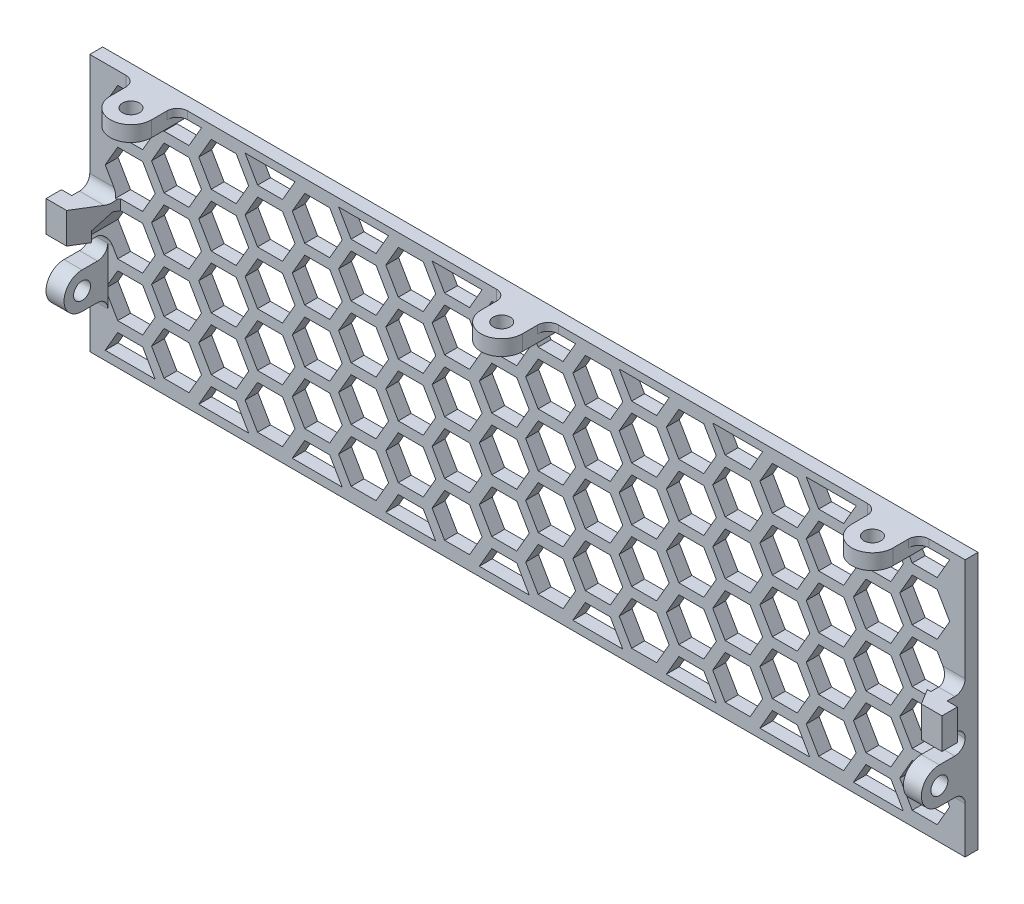
SolidWorks part; units mm, degrees
ref_plane "Plano frontal" through (0, 0, 0) normal (0, 0, 1) x (1, 0, 0)
ref_plane "Plano superior" through (0, 0, 0) normal (0, 1, 0) x (1, 0, 0)
ref_plane "Plano direito" through (0, 0, 0) normal (1, 0, 0) x (0, 0, -1)
sketch "Esboço1" plane through (0, 0, 0) normal (0, 0, 1) x (1, 0, 0)
  line L1 (-85, 25) -> (85, 25)
  line L2 (-85, 25) -> (-85, -25)
  line L3 (-85, -25) -> (85, -25)
  line L4 (85, 25) -> (85, -25)
  line L5 (-85, 25) -> (85, -25) construction
  line L6 (-85, -25) -> (85, 25) construction
  point P0 (0, 0)
  dimension "D1" = 170
  dimension "D2" = 50
extrude "Ressalto-extrusão1" add sketch "Esboço1" along normal blind 2.5
sketch "Esboço2" plane through (0, 0, 0) normal (0, 1, 0) x (1, 0, 0)
  line L0 (-85, -2.5) -> (-85, -6)
  line L1 (-85, -6) -> (-87, -6)
  line L2 (-87, -6) -> (-87, -9)
  line L3 (-87, -9) -> (-83, -9)
  line L4 (-83, -9) -> (-79, -2.5)
  line L5 (85, -2.5) -> (-85, -2.5) construction
  line L6 (85, 0) -> (-85, 0) construction
  line L7 (-83, -9) -> (-83, -2.5) construction
  line L8 (-83, -2.5) -> (-79, -2.5) construction
  line L9 (-85, -2.5) -> (-79, -2.5)
  line L10 (0, 0) -> (0, -20.2439) construction
  line L11 (83, -2.5) -> (79, -2.5) construction
  line L12 (83, -9) -> (83, -2.5) construction
  line L13 (85, -2.5) -> (79, -2.5)
  line L14 (83, -9) -> (79, -2.5)
  line L15 (87, -9) -> (83, -9)
  line L16 (87, -6) -> (87, -9)
  line L17 (85, -6) -> (87, -6)
  line L18 (85, -2.5) -> (85, -6)
  point P10 (-87, -7.5)
  dimension "D1" = 7.5
  dimension "D2" = 2
  dimension "D3" = 3
  dimension "D4" = 2
  dimension "D5" = 4
extrude "Ressalto-extrusão2" add sketch "Esboço2" along normal mid plane 6
sketch "Esboço3" plane through (0, 0, 0) normal (0, 0, -1) x (-1, 0, 0)
  line L0 (-72.3051, 23.5) -> (-70.5763, 22.5019) construction
  line L4 (-82, 23.5) -> (-79.5763, 19.302)
  line L5 (-79.5763, 19.302) -> (-74.7288, 19.302)
  line L6 (-74.7288, 19.302) -> (-72.3051, 23.5)
  line L7 (-63.3051, 18.3038) -> (-65.7288, 22.5019)
  line L8 (-65.7288, 22.5019) -> (-70.5763, 22.5019)
  line L9 (-70.5763, 22.5019) -> (-73, 18.3038)
  line L10 (-73, 18.3038) -> (-70.5763, 14.1058)
  line L11 (-70.5763, 14.1058) -> (-65.7288, 14.1058)
  line L12 (-65.7288, 14.1058) -> (-63.3051, 18.3038)
  line L13 (-85, 25) -> (85, 25) construction
  line L14 (63.3051, 23.5) -> (73, 23.5)
  line L15 (-73, 18.3038) -> (-80.4849, 18.3038) construction
  line L19 (-63.8369, 23.5) -> (-61.4131, 19.302)
  line L20 (-61.4131, 19.302) -> (-56.5657, 19.302)
  line L21 (-56.5657, 19.302) -> (-54.142, 23.5)
  line L22 (-45.142, 18.3038) -> (-47.5657, 22.5019)
  line L23 (-47.5657, 22.5019) -> (-52.4131, 22.5019)
  line L24 (-52.4131, 22.5019) -> (-54.8369, 18.3038)
  line L25 (-54.8369, 18.3038) -> (-52.4131, 14.1058)
  line L26 (-52.4131, 14.1058) -> (-47.5657, 14.1058)
  line L27 (-47.5657, 14.1058) -> (-45.142, 18.3038)
  line L31 (-45.6737, 23.5) -> (-43.25, 19.302)
  line L32 (-43.25, 19.302) -> (-38.4026, 19.302)
  line L33 (-38.4026, 19.302) -> (-35.9788, 23.5)
  line L34 (-26.9788, 18.3038) -> (-29.4026, 22.5019)
  line L35 (-29.4026, 22.5019) -> (-34.25, 22.5019)
  line L36 (-34.25, 22.5019) -> (-36.6737, 18.3038)
  line L37 (-36.6737, 18.3038) -> (-34.25, 14.1058)
  line L38 (-34.25, 14.1058) -> (-29.4026, 14.1058)
  line L39 (-29.4026, 14.1058) -> (-26.9788, 18.3038)
  line L43 (-27.5106, 23.5) -> (-25.0869, 19.302)
  line L44 (-25.0869, 19.302) -> (-20.2394, 19.302)
  line L45 (-20.2394, 19.302) -> (-17.8157, 23.5)
  line L46 (-8.8157, 18.3038) -> (-11.2394, 22.5019)
  line L47 (-11.2394, 22.5019) -> (-16.0869, 22.5019)
  line L48 (-16.0869, 22.5019) -> (-18.5106, 18.3038)
  line L49 (-18.5106, 18.3038) -> (-16.0869, 14.1058)
  line L50 (-16.0869, 14.1058) -> (-11.2394, 14.1058)
  line L51 (-11.2394, 14.1058) -> (-8.8157, 18.3038)
  line L55 (-9.3474, 23.5) -> (-6.9237, 19.302)
  line L56 (-6.9237, 19.302) -> (-2.0763, 19.302)
  line L57 (-2.0763, 19.302) -> (0.3474, 23.5)
  line L58 (9.3474, 18.3038) -> (6.9237, 22.5019)
  line L59 (6.9237, 22.5019) -> (2.0763, 22.5019)
  line L60 (2.0763, 22.5019) -> (-0.3474, 18.3038)
  line L61 (-0.3474, 18.3038) -> (2.0763, 14.1058)
  line L62 (2.0763, 14.1058) -> (6.9237, 14.1058)
  line L63 (6.9237, 14.1058) -> (9.3474, 18.3038)
  line L67 (8.8157, 23.5) -> (11.2394, 19.302)
  line L68 (11.2394, 19.302) -> (16.0869, 19.302)
  line L69 (16.0869, 19.302) -> (18.5106, 23.5)
  line L70 (27.5106, 18.3038) -> (25.0869, 22.5019)
  line L71 (25.0869, 22.5019) -> (20.2394, 22.5019)
  line L72 (20.2394, 22.5019) -> (17.8157, 18.3038)
  line L73 (17.8157, 18.3038) -> (20.2394, 14.1058)
  line L74 (20.2394, 14.1058) -> (25.0869, 14.1058)
  line L75 (25.0869, 14.1058) -> (27.5106, 18.3038)
  line L79 (26.9788, 23.5) -> (29.4026, 19.302)
  line L80 (29.4026, 19.302) -> (34.25, 19.302)
  line L81 (34.25, 19.302) -> (36.6737, 23.5)
  line L82 (45.6737, 18.3038) -> (43.25, 22.5019)
  line L83 (43.25, 22.5019) -> (38.4026, 22.5019)
  line L84 (38.4026, 22.5019) -> (35.9788, 18.3038)
  line L85 (35.9788, 18.3038) -> (38.4026, 14.1058)
  line L86 (38.4026, 14.1058) -> (43.25, 14.1058)
  line L87 (43.25, 14.1058) -> (45.6737, 18.3038)
  line L91 (45.142, 23.5) -> (47.5657, 19.302)
  line L92 (47.5657, 19.302) -> (52.4131, 19.302)
  line L93 (52.4131, 19.302) -> (54.8369, 23.5)
  line L94 (63.8369, 18.3038) -> (61.4131, 22.5019)
  line L95 (61.4131, 22.5019) -> (56.5657, 22.5019)
  line L96 (56.5657, 22.5019) -> (54.142, 18.3038)
  line L97 (54.142, 18.3038) -> (56.5657, 14.1058)
  line L98 (56.5657, 14.1058) -> (61.4131, 14.1058)
  line L99 (61.4131, 14.1058) -> (63.8369, 18.3038)
  line L103 (63.3051, 23.5) -> (65.7288, 19.302)
  line L104 (65.7288, 19.302) -> (70.5763, 19.302)
  line L105 (70.5763, 19.302) -> (73, 23.5)
  line L106 (82, 18.3038) -> (79.5763, 22.5019)
  line L107 (79.5763, 22.5019) -> (74.7288, 22.5019)
  line L108 (74.7288, 22.5019) -> (72.3051, 18.3038)
  line L109 (72.3051, 18.3038) -> (74.7288, 14.1058)
  line L110 (74.7288, 14.1058) -> (79.5763, 14.1058)
  line L111 (79.5763, 14.1058) -> (82, 18.3038)
  line L112 (-54.142, 13.1077) -> (-56.5657, 17.3057)
  line L113 (-56.5657, 17.3057) -> (-61.4131, 17.3057)
  line L114 (-61.4131, 17.3057) -> (-63.8369, 13.1077)
  line L115 (-63.8369, 13.1077) -> (-61.4131, 8.9097)
  line L116 (-61.4131, 8.9097) -> (-56.5657, 8.9097)
  line L117 (-56.5657, 8.9097) -> (-54.142, 13.1077)
  line L118 (-45.142, 7.9115) -> (-47.5657, 12.1095)
  line L119 (-47.5657, 12.1095) -> (-52.4131, 12.1095)
  line L120 (-52.4131, 12.1095) -> (-54.8369, 7.9115)
  line L121 (-54.8369, 7.9115) -> (-52.4131, 3.7135)
  line L122 (-52.4131, 3.7135) -> (-47.5657, 3.7135)
  line L123 (-47.5657, 3.7135) -> (-45.142, 7.9115)
  line L124 (-35.9788, 13.1077) -> (-38.4026, 17.3057)
  line L125 (-38.4026, 17.3057) -> (-43.25, 17.3057)
  line L126 (-43.25, 17.3057) -> (-45.6737, 13.1077)
  line L127 (-45.6737, 13.1077) -> (-43.25, 8.9097)
  line L128 (-43.25, 8.9097) -> (-38.4026, 8.9097)
  line L129 (-38.4026, 8.9097) -> (-35.9788, 13.1077)
  line L130 (-26.9788, 7.9115) -> (-29.4026, 12.1095)
  line L131 (-29.4026, 12.1095) -> (-34.25, 12.1095)
  line L132 (-34.25, 12.1095) -> (-36.6737, 7.9115)
  line L133 (-36.6737, 7.9115) -> (-34.25, 3.7135)
  line L134 (-34.25, 3.7135) -> (-29.4026, 3.7135)
  line L135 (-29.4026, 3.7135) -> (-26.9788, 7.9115)
  line L136 (-17.8157, 13.1077) -> (-20.2394, 17.3057)
  line L137 (-20.2394, 17.3057) -> (-25.0869, 17.3057)
  line L138 (-25.0869, 17.3057) -> (-27.5106, 13.1077)
  line L139 (-27.5106, 13.1077) -> (-25.0869, 8.9097)
  line L140 (-25.0869, 8.9097) -> (-20.2394, 8.9097)
  line L141 (-20.2394, 8.9097) -> (-17.8157, 13.1077)
  line L142 (-8.8157, 7.9115) -> (-11.2394, 12.1095)
  line L143 (-11.2394, 12.1095) -> (-16.0869, 12.1095)
  line L144 (-16.0869, 12.1095) -> (-18.5106, 7.9115)
  line L145 (-18.5106, 7.9115) -> (-16.0869, 3.7135)
  line L146 (-16.0869, 3.7135) -> (-11.2394, 3.7135)
  line L147 (-11.2394, 3.7135) -> (-8.8157, 7.9115)
  line L148 (0.3474, 13.1077) -> (-2.0763, 17.3057)
  line L149 (-2.0763, 17.3057) -> (-6.9237, 17.3057)
  line L150 (-6.9237, 17.3057) -> (-9.3474, 13.1077)
  line L151 (-9.3474, 13.1077) -> (-6.9237, 8.9097)
  line L152 (-6.9237, 8.9097) -> (-2.0763, 8.9097)
  line L153 (-2.0763, 8.9097) -> (0.3474, 13.1077)
  line L154 (9.3474, 7.9115) -> (6.9237, 12.1095)
  line L155 (6.9237, 12.1095) -> (2.0763, 12.1095)
  line L156 (2.0763, 12.1095) -> (-0.3474, 7.9115)
  line L157 (-0.3474, 7.9115) -> (2.0763, 3.7135)
  line L158 (2.0763, 3.7135) -> (6.9237, 3.7135)
  line L159 (6.9237, 3.7135) -> (9.3474, 7.9115)
  line L160 (18.5106, 13.1077) -> (16.0869, 17.3057)
  line L161 (16.0869, 17.3057) -> (11.2394, 17.3057)
  line L162 (11.2394, 17.3057) -> (8.8157, 13.1077)
  line L163 (8.8157, 13.1077) -> (11.2394, 8.9097)
  line L164 (11.2394, 8.9097) -> (16.0869, 8.9097)
  line L165 (16.0869, 8.9097) -> (18.5106, 13.1077)
  line L166 (27.5106, 7.9115) -> (25.0869, 12.1095)
  line L167 (25.0869, 12.1095) -> (20.2394, 12.1095)
  line L168 (20.2394, 12.1095) -> (17.8157, 7.9115)
  line L169 (17.8157, 7.9115) -> (20.2394, 3.7135)
  line L170 (20.2394, 3.7135) -> (25.0869, 3.7135)
  line L171 (25.0869, 3.7135) -> (27.5106, 7.9115)
  line L172 (36.6737, 13.1077) -> (34.25, 17.3057)
  line L173 (34.25, 17.3057) -> (29.4026, 17.3057)
  line L174 (29.4026, 17.3057) -> (26.9788, 13.1077)
  line L175 (26.9788, 13.1077) -> (29.4026, 8.9097)
  line L176 (29.4026, 8.9097) -> (34.25, 8.9097)
  line L177 (34.25, 8.9097) -> (36.6737, 13.1077)
  line L178 (45.6737, 7.9115) -> (43.25, 12.1095)
  line L179 (43.25, 12.1095) -> (38.4026, 12.1095)
  line L180 (38.4026, 12.1095) -> (35.9788, 7.9115)
  line L181 (35.9788, 7.9115) -> (38.4026, 3.7135)
  line L182 (38.4026, 3.7135) -> (43.25, 3.7135)
  line L183 (43.25, 3.7135) -> (45.6737, 7.9115)
  line L184 (54.8369, 13.1077) -> (52.4131, 17.3057)
  line L185 (52.4131, 17.3057) -> (47.5657, 17.3057)
  line L186 (47.5657, 17.3057) -> (45.142, 13.1077)
  line L187 (45.142, 13.1077) -> (47.5657, 8.9097)
  line L188 (47.5657, 8.9097) -> (52.4131, 8.9097)
  line L189 (52.4131, 8.9097) -> (54.8369, 13.1077)
  line L190 (63.8369, 7.9115) -> (61.4131, 12.1095)
  line L191 (61.4131, 12.1095) -> (56.5657, 12.1095)
  line L192 (56.5657, 12.1095) -> (54.142, 7.9115)
  line L193 (54.142, 7.9115) -> (56.5657, 3.7135)
  line L194 (56.5657, 3.7135) -> (61.4131, 3.7135)
  line L195 (61.4131, 3.7135) -> (63.8369, 7.9115)
  line L196 (73, 13.1077) -> (70.5763, 17.3057)
  line L197 (70.5763, 17.3057) -> (65.7288, 17.3057)
  line L198 (65.7288, 17.3057) -> (63.3051, 13.1077)
  line L199 (63.3051, 13.1077) -> (65.7288, 8.9097)
  line L200 (65.7288, 8.9097) -> (70.5763, 8.9097)
  line L201 (70.5763, 8.9097) -> (73, 13.1077)
  line L202 (82, 7.9115) -> (79.5763, 12.1095)
  line L203 (79.5763, 12.1095) -> (74.7288, 12.1095)
  line L204 (74.7288, 12.1095) -> (72.3051, 7.9115)
  line L205 (72.3051, 7.9115) -> (74.7288, 3.7135)
  line L206 (74.7288, 3.7135) -> (79.5763, 3.7135)
  line L207 (79.5763, 3.7135) -> (82, 7.9115)
  line L208 (-54.142, 2.7154) -> (-56.5657, 6.9134)
  line L209 (-56.5657, 6.9134) -> (-61.4131, 6.9134)
  line L210 (-61.4131, 6.9134) -> (-63.8369, 2.7154)
  line L211 (-63.8369, 2.7154) -> (-61.4131, -1.4826)
  line L212 (-61.4131, -1.4826) -> (-56.5657, -1.4826)
  line L213 (-56.5657, -1.4826) -> (-54.142, 2.7154)
  line L214 (-45.142, -2.4808) -> (-47.5657, 1.7172)
  line L215 (-47.5657, 1.7172) -> (-52.4131, 1.7172)
  line L216 (-52.4131, 1.7172) -> (-54.8369, -2.4808)
  line L217 (-54.8369, -2.4808) -> (-52.4131, -6.6788)
  line L218 (-52.4131, -6.6788) -> (-47.5657, -6.6788)
  line L219 (-47.5657, -6.6788) -> (-45.142, -2.4808)
  line L220 (-35.9788, 2.7154) -> (-38.4026, 6.9134)
  line L221 (-38.4026, 6.9134) -> (-43.25, 6.9134)
  line L222 (-43.25, 6.9134) -> (-45.6737, 2.7154)
  line L223 (-45.6737, 2.7154) -> (-43.25, -1.4826)
  line L224 (-43.25, -1.4826) -> (-38.4026, -1.4826)
  line L225 (-38.4026, -1.4826) -> (-35.9788, 2.7154)
  line L226 (-26.9788, -2.4808) -> (-29.4026, 1.7172)
  line L227 (-29.4026, 1.7172) -> (-34.25, 1.7172)
  line L228 (-34.25, 1.7172) -> (-36.6737, -2.4808)
  line L229 (-36.6737, -2.4808) -> (-34.25, -6.6788)
  line L230 (-34.25, -6.6788) -> (-29.4026, -6.6788)
  line L231 (-29.4026, -6.6788) -> (-26.9788, -2.4808)
  line L232 (-17.8157, 2.7154) -> (-20.2394, 6.9134)
  line L233 (-20.2394, 6.9134) -> (-25.0869, 6.9134)
  line L234 (-25.0869, 6.9134) -> (-27.5106, 2.7154)
  line L235 (-27.5106, 2.7154) -> (-25.0869, -1.4826)
  line L236 (-25.0869, -1.4826) -> (-20.2394, -1.4826)
  line L237 (-20.2394, -1.4826) -> (-17.8157, 2.7154)
  line L238 (-8.8157, -2.4808) -> (-11.2394, 1.7172)
  line L239 (-11.2394, 1.7172) -> (-16.0869, 1.7172)
  line L240 (-16.0869, 1.7172) -> (-18.5106, -2.4808)
  line L241 (-18.5106, -2.4808) -> (-16.0869, -6.6788)
  line L242 (-16.0869, -6.6788) -> (-11.2394, -6.6788)
  line L243 (-11.2394, -6.6788) -> (-8.8157, -2.4808)
  line L244 (0.3474, 2.7154) -> (-2.0763, 6.9134)
  line L245 (-2.0763, 6.9134) -> (-6.9237, 6.9134)
  line L246 (-6.9237, 6.9134) -> (-9.3474, 2.7154)
  line L247 (-9.3474, 2.7154) -> (-6.9237, -1.4826)
  line L248 (-6.9237, -1.4826) -> (-2.0763, -1.4826)
  line L249 (-2.0763, -1.4826) -> (0.3474, 2.7154)
  line L250 (9.3474, -2.4808) -> (6.9237, 1.7172)
  line L251 (6.9237, 1.7172) -> (2.0763, 1.7172)
  line L252 (2.0763, 1.7172) -> (-0.3474, -2.4808)
  line L253 (-0.3474, -2.4808) -> (2.0763, -6.6788)
  line L254 (2.0763, -6.6788) -> (6.9237, -6.6788)
  line L255 (6.9237, -6.6788) -> (9.3474, -2.4808)
  line L256 (18.5106, 2.7154) -> (16.0869, 6.9134)
  line L257 (16.0869, 6.9134) -> (11.2394, 6.9134)
  line L258 (11.2394, 6.9134) -> (8.8157, 2.7154)
  line L259 (8.8157, 2.7154) -> (11.2394, -1.4826)
  line L260 (11.2394, -1.4826) -> (16.0869, -1.4826)
  line L261 (16.0869, -1.4826) -> (18.5106, 2.7154)
  line L262 (27.5106, -2.4808) -> (25.0869, 1.7172)
  line L263 (25.0869, 1.7172) -> (20.2394, 1.7172)
  line L264 (20.2394, 1.7172) -> (17.8157, -2.4808)
  line L265 (17.8157, -2.4808) -> (20.2394, -6.6788)
  line L266 (20.2394, -6.6788) -> (25.0869, -6.6788)
  line L267 (25.0869, -6.6788) -> (27.5106, -2.4808)
  line L268 (36.6737, 2.7154) -> (34.25, 6.9134)
  line L269 (34.25, 6.9134) -> (29.4026, 6.9134)
  line L270 (29.4026, 6.9134) -> (26.9788, 2.7154)
  line L271 (26.9788, 2.7154) -> (29.4026, -1.4826)
  line L272 (29.4026, -1.4826) -> (34.25, -1.4826)
  line L273 (34.25, -1.4826) -> (36.6737, 2.7154)
  line L274 (45.6737, -2.4808) -> (43.25, 1.7172)
  line L275 (43.25, 1.7172) -> (38.4026, 1.7172)
  line L276 (38.4026, 1.7172) -> (35.9788, -2.4808)
  line L277 (35.9788, -2.4808) -> (38.4026, -6.6788)
  line L278 (38.4026, -6.6788) -> (43.25, -6.6788)
  line L279 (43.25, -6.6788) -> (45.6737, -2.4808)
  line L280 (54.8369, 2.7154) -> (52.4131, 6.9134)
  line L281 (52.4131, 6.9134) -> (47.5657, 6.9134)
  line L282 (47.5657, 6.9134) -> (45.142, 2.7154)
  line L283 (45.142, 2.7154) -> (47.5657, -1.4826)
  line L284 (47.5657, -1.4826) -> (52.4131, -1.4826)
  line L285 (52.4131, -1.4826) -> (54.8369, 2.7154)
  line L286 (63.8369, -2.4808) -> (61.4131, 1.7172)
  line L287 (61.4131, 1.7172) -> (56.5657, 1.7172)
  line L288 (56.5657, 1.7172) -> (54.142, -2.4808)
  line L289 (54.142, -2.4808) -> (56.5657, -6.6788)
  line L290 (56.5657, -6.6788) -> (61.4131, -6.6788)
  line L291 (61.4131, -6.6788) -> (63.8369, -2.4808)
  line L292 (73, 2.7154) -> (70.5763, 6.9134)
  line L293 (70.5763, 6.9134) -> (65.7288, 6.9134)
  line L294 (65.7288, 6.9134) -> (63.3051, 2.7154)
  line L295 (63.3051, 2.7154) -> (65.7288, -1.4826)
  line L296 (65.7288, -1.4826) -> (70.5763, -1.4826)
  line L297 (70.5763, -1.4826) -> (73, 2.7154)
  line L298 (82, -2.4808) -> (79.5763, 1.7172)
  line L299 (79.5763, 1.7172) -> (74.7288, 1.7172)
  line L300 (74.7288, 1.7172) -> (72.3051, -2.4808)
  line L301 (72.3051, -2.4808) -> (74.7288, -6.6788)
  line L302 (74.7288, -6.6788) -> (79.5763, -6.6788)
  line L303 (79.5763, -6.6788) -> (82, -2.4808)
  line L304 (-54.142, -7.6769) -> (-56.5657, -3.4789)
  line L305 (-56.5657, -3.4789) -> (-61.4131, -3.4789)
  line L306 (-61.4131, -3.4789) -> (-63.8369, -7.6769)
  line L307 (-63.8369, -7.6769) -> (-61.4131, -11.8749)
  line L308 (-61.4131, -11.8749) -> (-56.5657, -11.8749)
  line L309 (-56.5657, -11.8749) -> (-54.142, -7.6769)
  line L310 (-45.142, -12.8731) -> (-47.5657, -8.6751)
  line L311 (-47.5657, -8.6751) -> (-52.4131, -8.6751)
  line L312 (-52.4131, -8.6751) -> (-54.8369, -12.8731)
  line L313 (-54.8369, -12.8731) -> (-52.4131, -17.0711)
  line L314 (-52.4131, -17.0711) -> (-47.5657, -17.0711)
  line L315 (-47.5657, -17.0711) -> (-45.142, -12.8731)
  line L316 (-35.9788, -7.6769) -> (-38.4026, -3.4789)
  line L317 (-38.4026, -3.4789) -> (-43.25, -3.4789)
  line L318 (-43.25, -3.4789) -> (-45.6737, -7.6769)
  line L319 (-45.6737, -7.6769) -> (-43.25, -11.8749)
  line L320 (-43.25, -11.8749) -> (-38.4026, -11.8749)
  line L321 (-38.4026, -11.8749) -> (-35.9788, -7.6769)
  line L322 (-26.9788, -12.8731) -> (-29.4026, -8.6751)
  line L323 (-29.4026, -8.6751) -> (-34.25, -8.6751)
  line L324 (-34.25, -8.6751) -> (-36.6737, -12.8731)
  line L325 (-36.6737, -12.8731) -> (-34.25, -17.0711)
  line L326 (-34.25, -17.0711) -> (-29.4026, -17.0711)
  line L327 (-29.4026, -17.0711) -> (-26.9788, -12.8731)
  line L328 (-17.8157, -7.6769) -> (-20.2394, -3.4789)
  line L329 (-20.2394, -3.4789) -> (-25.0869, -3.4789)
  line L330 (-25.0869, -3.4789) -> (-27.5106, -7.6769)
  line L331 (-27.5106, -7.6769) -> (-25.0869, -11.8749)
  line L332 (-25.0869, -11.8749) -> (-20.2394, -11.8749)
  line L333 (-20.2394, -11.8749) -> (-17.8157, -7.6769)
  line L334 (-8.8157, -12.8731) -> (-11.2394, -8.6751)
  line L335 (-11.2394, -8.6751) -> (-16.0869, -8.6751)
  line L336 (-16.0869, -8.6751) -> (-18.5106, -12.8731)
  line L337 (-18.5106, -12.8731) -> (-16.0869, -17.0711)
  line L338 (-16.0869, -17.0711) -> (-11.2394, -17.0711)
  line L339 (-11.2394, -17.0711) -> (-8.8157, -12.8731)
  line L340 (0.3474, -7.6769) -> (-2.0763, -3.4789)
  line L341 (-2.0763, -3.4789) -> (-6.9237, -3.4789)
  line L342 (-6.9237, -3.4789) -> (-9.3474, -7.6769)
  line L343 (-9.3474, -7.6769) -> (-6.9237, -11.8749)
  line L344 (-6.9237, -11.8749) -> (-2.0763, -11.8749)
  line L345 (-2.0763, -11.8749) -> (0.3474, -7.6769)
  line L346 (9.3474, -12.8731) -> (6.9237, -8.6751)
  line L347 (6.9237, -8.6751) -> (2.0763, -8.6751)
  line L348 (2.0763, -8.6751) -> (-0.3474, -12.8731)
  line L349 (-0.3474, -12.8731) -> (2.0763, -17.0711)
  line L350 (2.0763, -17.0711) -> (6.9237, -17.0711)
  line L351 (6.9237, -17.0711) -> (9.3474, -12.8731)
  line L352 (18.5106, -7.6769) -> (16.0869, -3.4789)
  line L353 (16.0869, -3.4789) -> (11.2394, -3.4789)
  line L354 (11.2394, -3.4789) -> (8.8157, -7.6769)
  line L355 (8.8157, -7.6769) -> (11.2394, -11.8749)
  line L356 (11.2394, -11.8749) -> (16.0869, -11.8749)
  line L357 (16.0869, -11.8749) -> (18.5106, -7.6769)
  line L358 (27.5106, -12.8731) -> (25.0869, -8.6751)
  line L359 (25.0869, -8.6751) -> (20.2394, -8.6751)
  line L360 (20.2394, -8.6751) -> (17.8157, -12.8731)
  line L361 (17.8157, -12.8731) -> (20.2394, -17.0711)
  line L362 (20.2394, -17.0711) -> (25.0869, -17.0711)
  line L363 (25.0869, -17.0711) -> (27.5106, -12.8731)
  line L364 (36.6737, -7.6769) -> (34.25, -3.4789)
  line L365 (34.25, -3.4789) -> (29.4026, -3.4789)
  line L366 (29.4026, -3.4789) -> (26.9788, -7.6769)
  line L367 (26.9788, -7.6769) -> (29.4026, -11.8749)
  line L368 (29.4026, -11.8749) -> (34.25, -11.8749)
  line L369 (34.25, -11.8749) -> (36.6737, -7.6769)
  line L370 (45.6737, -12.8731) -> (43.25, -8.6751)
  line L371 (43.25, -8.6751) -> (38.4026, -8.6751)
  line L372 (38.4026, -8.6751) -> (35.9788, -12.8731)
  line L373 (35.9788, -12.8731) -> (38.4026, -17.0711)
  line L374 (38.4026, -17.0711) -> (43.25, -17.0711)
  line L375 (43.25, -17.0711) -> (45.6737, -12.8731)
  line L376 (54.8369, -7.6769) -> (52.4131, -3.4789)
  line L377 (52.4131, -3.4789) -> (47.5657, -3.4789)
  line L378 (47.5657, -3.4789) -> (45.142, -7.6769)
  line L379 (45.142, -7.6769) -> (47.5657, -11.8749)
  line L380 (47.5657, -11.8749) -> (52.4131, -11.8749)
  line L381 (52.4131, -11.8749) -> (54.8369, -7.6769)
  line L382 (63.8369, -12.8731) -> (61.4131, -8.6751)
  line L383 (61.4131, -8.6751) -> (56.5657, -8.6751)
  line L384 (56.5657, -8.6751) -> (54.142, -12.8731)
  line L385 (54.142, -12.8731) -> (56.5657, -17.0711)
  line L386 (56.5657, -17.0711) -> (61.4131, -17.0711)
  line L387 (61.4131, -17.0711) -> (63.8369, -12.8731)
  line L388 (73, -7.6769) -> (70.5763, -3.4789)
  line L389 (70.5763, -3.4789) -> (65.7288, -3.4789)
  line L390 (65.7288, -3.4789) -> (63.3051, -7.6769)
  line L391 (63.3051, -7.6769) -> (65.7288, -11.8749)
  line L392 (65.7288, -11.8749) -> (70.5763, -11.8749)
  line L393 (70.5763, -11.8749) -> (73, -7.6769)
  line L394 (82, -12.8731) -> (79.5763, -8.6751)
  line L395 (79.5763, -8.6751) -> (74.7288, -8.6751)
  line L396 (74.7288, -8.6751) -> (72.3051, -12.8731)
  line L397 (72.3051, -12.8731) -> (74.7288, -17.0711)
  line L398 (74.7288, -17.0711) -> (79.5763, -17.0711)
  line L399 (79.5763, -17.0711) -> (82, -12.8731)
  line L400 (-72.3051, 13.1077) -> (-74.7288, 17.3057)
  line L401 (-74.7288, 17.3057) -> (-79.5763, 17.3057)
  line L402 (-79.5763, 17.3057) -> (-82, 13.1077)
  line L403 (-82, 13.1077) -> (-79.5763, 8.9097)
  line L404 (-79.5763, 8.9097) -> (-74.7288, 8.9097)
  line L405 (-74.7288, 8.9097) -> (-72.3051, 13.1077)
  line L406 (-63.3051, 7.9115) -> (-65.7288, 12.1095)
  line L407 (-65.7288, 12.1095) -> (-70.5763, 12.1095)
  line L408 (-70.5763, 12.1095) -> (-73, 7.9115)
  line L409 (-73, 7.9115) -> (-70.5763, 3.7135)
  line L410 (-70.5763, 3.7135) -> (-65.7288, 3.7135)
  line L411 (-65.7288, 3.7135) -> (-63.3051, 7.9115)
  line L412 (-72.3051, 2.7154) -> (-74.7288, 6.9134)
  line L413 (-74.7288, 6.9134) -> (-79.5763, 6.9134)
  line L414 (-79.5763, 6.9134) -> (-82, 2.7154)
  line L415 (-82, 2.7154) -> (-79.5763, -1.4826)
  line L416 (-79.5763, -1.4826) -> (-74.7288, -1.4826)
  line L417 (-74.7288, -1.4826) -> (-72.3051, 2.7154)
  line L418 (-63.3051, -2.4808) -> (-65.7288, 1.7172)
  line L419 (-65.7288, 1.7172) -> (-70.5763, 1.7172)
  line L420 (-70.5763, 1.7172) -> (-73, -2.4808)
  line L421 (-73, -2.4808) -> (-70.5763, -6.6788)
  line L422 (-70.5763, -6.6788) -> (-65.7288, -6.6788)
  line L423 (-65.7288, -6.6788) -> (-63.3051, -2.4808)
  line L424 (-72.3051, -7.6769) -> (-74.7288, -3.4789)
  line L425 (-74.7288, -3.4789) -> (-79.5763, -3.4789)
  line L426 (-79.5763, -3.4789) -> (-82, -7.6769)
  line L427 (-82, -7.6769) -> (-79.5763, -11.8749)
  line L428 (-79.5763, -11.8749) -> (-74.7288, -11.8749)
  line L429 (-74.7288, -11.8749) -> (-72.3051, -7.6769)
  line L430 (-63.3051, -12.8731) -> (-65.7288, -8.6751)
  line L431 (-65.7288, -8.6751) -> (-70.5763, -8.6751)
  line L432 (-70.5763, -8.6751) -> (-73, -12.8731)
  line L433 (-73, -12.8731) -> (-70.5763, -17.0711)
  line L434 (-70.5763, -17.0711) -> (-65.7288, -17.0711)
  line L435 (-65.7288, -17.0711) -> (-63.3051, -12.8731)
  line L436 (-72.3051, -18.0692) -> (-74.7288, -13.8712)
  line L437 (-74.7288, -13.8712) -> (-79.5763, -13.8712)
  line L438 (-79.5763, -13.8712) -> (-82, -18.0692)
  line L439 (-82, -18.0692) -> (-79.5763, -22.2672)
  line L440 (-79.5763, -22.2672) -> (-74.7288, -22.2672)
  line L441 (-74.7288, -22.2672) -> (-72.3051, -18.0692)
  line L442 (-63.3051, -23.2654) -> (-65.7288, -19.0674)
  line L443 (-65.7288, -19.0674) -> (-70.5763, -19.0674)
  line L444 (-70.5763, -19.0674) -> (-73, -23.2654)
  line L448 (-54.142, -18.0692) -> (-56.5657, -13.8712)
  line L449 (-56.5657, -13.8712) -> (-61.4131, -13.8712)
  line L450 (-61.4131, -13.8712) -> (-63.8369, -18.0692)
  line L451 (-63.8369, -18.0692) -> (-61.4131, -22.2672)
  line L452 (-61.4131, -22.2672) -> (-56.5657, -22.2672)
  line L453 (-56.5657, -22.2672) -> (-54.142, -18.0692)
  line L454 (-45.142, -23.2654) -> (-47.5657, -19.0674)
  line L455 (-47.5657, -19.0674) -> (-52.4131, -19.0674)
  line L456 (-52.4131, -19.0674) -> (-54.8369, -23.2654)
  line L460 (-35.9788, -18.0692) -> (-38.4026, -13.8712)
  line L461 (-38.4026, -13.8712) -> (-43.25, -13.8712)
  line L462 (-43.25, -13.8712) -> (-45.6737, -18.0692)
  line L463 (-45.6737, -18.0692) -> (-43.25, -22.2672)
  line L464 (-43.25, -22.2672) -> (-38.4026, -22.2672)
  line L465 (-38.4026, -22.2672) -> (-35.9788, -18.0692)
  line L466 (-26.9788, -23.2654) -> (-29.4026, -19.0674)
  line L467 (-29.4026, -19.0674) -> (-34.25, -19.0674)
  line L468 (-34.25, -19.0674) -> (-36.6737, -23.2654)
  line L472 (-17.8157, -18.0692) -> (-20.2394, -13.8712)
  line L473 (-20.2394, -13.8712) -> (-25.0869, -13.8712)
  line L474 (-25.0869, -13.8712) -> (-27.5106, -18.0692)
  line L475 (-27.5106, -18.0692) -> (-25.0869, -22.2672)
  line L476 (-25.0869, -22.2672) -> (-20.2394, -22.2672)
  line L477 (-20.2394, -22.2672) -> (-17.8157, -18.0692)
  line L478 (-8.8157, -23.2654) -> (-11.2394, -19.0674)
  line L479 (-11.2394, -19.0674) -> (-16.0869, -19.0674)
  line L480 (-16.0869, -19.0674) -> (-18.5106, -23.2654)
  line L484 (0.3474, -18.0692) -> (-2.0763, -13.8712)
  line L485 (-2.0763, -13.8712) -> (-6.9237, -13.8712)
  line L486 (-6.9237, -13.8712) -> (-9.3474, -18.0692)
  line L487 (-9.3474, -18.0692) -> (-6.9237, -22.2672)
  line L488 (-6.9237, -22.2672) -> (-2.0763, -22.2672)
  line L489 (-2.0763, -22.2672) -> (0.3474, -18.0692)
  line L490 (9.3474, -23.2654) -> (6.9237, -19.0674)
  line L491 (6.9237, -19.0674) -> (2.0763, -19.0674)
  line L492 (2.0763, -19.0674) -> (-0.3474, -23.2654)
  line L496 (18.5106, -18.0692) -> (16.0869, -13.8712)
  line L497 (16.0869, -13.8712) -> (11.2394, -13.8712)
  line L498 (11.2394, -13.8712) -> (8.8157, -18.0692)
  line L499 (8.8157, -18.0692) -> (11.2394, -22.2672)
  line L500 (11.2394, -22.2672) -> (16.0869, -22.2672)
  line L501 (16.0869, -22.2672) -> (18.5106, -18.0692)
  line L502 (27.5106, -23.2654) -> (25.0869, -19.0674)
  line L503 (25.0869, -19.0674) -> (20.2394, -19.0674)
  line L504 (20.2394, -19.0674) -> (17.8157, -23.2654)
  line L508 (36.6737, -18.0692) -> (34.25, -13.8712)
  line L509 (34.25, -13.8712) -> (29.4026, -13.8712)
  line L510 (29.4026, -13.8712) -> (26.9788, -18.0692)
  line L511 (26.9788, -18.0692) -> (29.4026, -22.2672)
  line L512 (29.4026, -22.2672) -> (34.25, -22.2672)
  line L513 (34.25, -22.2672) -> (36.6737, -18.0692)
  line L514 (45.6737, -23.2654) -> (43.25, -19.0674)
  line L515 (43.25, -19.0674) -> (38.4026, -19.0674)
  line L516 (38.4026, -19.0674) -> (35.9788, -23.2654)
  line L520 (54.8369, -18.0692) -> (52.4131, -13.8712)
  line L521 (52.4131, -13.8712) -> (47.5657, -13.8712)
  line L522 (47.5657, -13.8712) -> (45.142, -18.0692)
  line L523 (45.142, -18.0692) -> (47.5657, -22.2672)
  line L524 (47.5657, -22.2672) -> (52.4131, -22.2672)
  line L525 (52.4131, -22.2672) -> (54.8369, -18.0692)
  line L526 (63.8369, -23.2654) -> (61.4131, -19.0674)
  line L527 (61.4131, -19.0674) -> (56.5657, -19.0674)
  line L528 (56.5657, -19.0674) -> (54.142, -23.2654)
  line L532 (73, -18.0692) -> (70.5763, -13.8712)
  line L533 (70.5763, -13.8712) -> (65.7288, -13.8712)
  line L534 (65.7288, -13.8712) -> (63.3051, -18.0692)
  line L535 (63.3051, -18.0692) -> (65.7288, -22.2672)
  line L536 (65.7288, -22.2672) -> (70.5763, -22.2672)
  line L537 (70.5763, -22.2672) -> (73, -18.0692)
  line L538 (82, -23.2654) -> (79.5763, -19.0674)
  line L539 (79.5763, -19.0674) -> (74.7288, -19.0674)
  line L540 (74.7288, -19.0674) -> (72.3051, -23.2654)
  line L544 (-82, 23.5) -> (-72.3051, 23.5)
  line L545 (-73, -23.2654) -> (-63.3051, -23.2654)
  line L546 (-82, 23.5) -> (-85, 23.5) construction
  line L547 (45.142, 23.5) -> (54.8369, 23.5)
  line L548 (26.9788, 23.5) -> (36.6737, 23.5)
  line L549 (8.8157, 23.5) -> (18.5106, 23.5)
  line L550 (-9.3474, 23.5) -> (0.3474, 23.5)
  line L551 (-27.5106, 23.5) -> (-17.8157, 23.5)
  line L552 (82, 18.3038) -> (85, 18.3038) construction
  line L553 (85, 25) -> (85, -25) construction
  line L554 (69.6025, -23.2654) -> (69.6025, -25) construction
  line L555 (-63.8369, 23.5) -> (-54.142, 23.5)
  line L556 (-45.6737, 23.5) -> (-35.9788, 23.5)
  line L557 (-85, -25) -> (-85, 25) construction
  line L558 (-54.8369, -23.2654) -> (-45.142, -23.2654)
  line L559 (-36.6737, -23.2654) -> (-26.9788, -23.2654)
  line L560 (85, -25) -> (-85, -25) construction
  line L561 (-74.7288, 27.698) -> (-79.5763, 27.698) [skipped]
  line L562 (-80.7881, 25.599) -> (-82, 23.5) [skipped]
  line L563 (-72.3051, 23.5) -> (-73.517, 25.599) [skipped]
  line L564 (-73, -23.2654) -> (-70.5763, -27.4634) [skipped]
  line L565 (-65.7288, -27.4634) -> (-63.3051, -23.2654) [skipped]
  line L566 (-70.5763, -27.4634) -> (-65.7288, -27.4634) [skipped]
  line L567 (-54.8369, -23.2654) -> (-52.4131, -27.4634) [skipped]
  line L568 (-52.4131, -27.4634) -> (-47.5657, -27.4634) [skipped]
  line L569 (-47.5657, -27.4634) -> (-45.142, -23.2654) [skipped]
  line L570 (-36.6737, -23.2654) -> (-34.25, -27.4634) [skipped]
  line L571 (-34.25, -27.4634) -> (-29.4026, -27.4634) [skipped]
  line L572 (-29.4026, -27.4634) -> (-26.9788, -23.2654) [skipped]
  line L573 (-18.5106, -23.2654) -> (-8.8157, -23.2654)
  line L574 (-18.5106, -23.2654) -> (-16.0869, -27.4634) [skipped]
  line L575 (-16.0869, -27.4634) -> (-11.2394, -27.4634) [skipped]
  line L576 (-11.2394, -27.4634) -> (-8.8157, -23.2654) [skipped]
  line L577 (-0.3474, -23.2654) -> (9.3474, -23.2654)
  line L578 (-0.3474, -23.2654) -> (2.0763, -27.4634) [skipped]
  line L579 (6.9237, -27.4634) -> (9.3474, -23.2654) [skipped]
  line L580 (2.0763, -27.4634) -> (6.9237, -27.4634) [skipped]
  line L581 (17.8157, -23.2654) -> (20.2394, -27.4634) [skipped]
  line L582 (20.2394, -27.4634) -> (25.0869, -27.4634) [skipped]
  line L583 (25.0869, -27.4634) -> (27.5106, -23.2654) [skipped]
  line L584 (35.9788, -23.2654) -> (38.4026, -27.4634) [skipped]
  line L585 (38.4026, -27.4634) -> (43.25, -27.4634) [skipped]
  line L586 (43.25, -27.4634) -> (45.6737, -23.2654) [skipped]
  line L587 (54.142, -23.2654) -> (56.5657, -27.4634) [skipped]
  line L588 (56.5657, -27.4634) -> (61.4131, -27.4634) [skipped]
  line L589 (61.4131, -27.4634) -> (63.8369, -23.2654) [skipped]
  line L590 (72.3051, -23.2654) -> (74.7288, -27.4634) [skipped]
  line L591 (74.7288, -27.4634) -> (79.5763, -27.4634) [skipped]
  line L592 (79.5763, -27.4634) -> (82, -23.2654) [skipped]
  line L593 (72.3051, -23.2654) -> (82, -23.2654)
  line L594 (54.142, -23.2654) -> (63.8369, -23.2654)
  line L595 (17.8157, -23.2654) -> (27.5106, -23.2654)
  line L596 (35.9788, -23.2654) -> (45.6737, -23.2654)
  arc A0 (-81.3506, 23.5) -> (-72.9546, 23.5) centre (-77.1526, 23.5) ccw construction
  circle A1 centre (-68.1526, 18.3038) radius 4.198 construction
  point P1 (-81.1188, 25)
  point P8 (0, 0)
  point P23 (0, 0)
  point P24 (0, 0)
  point P553 (-85, 22.4942)
  point P556 (-68.2093, 25)
  point P557 (-65.1134, 25)
  point P558 (69.6025, -25)
  point P561 (-64.9087, 25)
  point P563 (-76.8625, 23.5)
  point P564 (-65.7829, 23.3827)
  point P565 (-81.5579, 23.3827)
  point P566 (-76.5, 23.3827)
  point P567 (-76.5, 23.3827)
  point P568 (-101.969, 31.2067)
  point P569 (-81.1188, 25)
  point P570 (-76.5, 23.3827)
  point P571 (0, 0)
  point P572 (0, 0)
  dimension "D1" = 1.5
  dimension "D2" = 9
  dimension "D3" = 3
  dimension "D7" = 9
  dimension "D8" = 5
extrude "Corte-extrusão1" cut sketch "Esboço3" against normal blind 6
sketch "Esboço4" plane through (0, 25, 0) normal (0, 1, 0) x (1, 0, 0)
  line L0 (-4, -7.5) -> (-4, 0)
  line L2 (-4, 0) -> (4, 0)
  line L3 (4, 0) -> (4, -7.5)
  line L4 (-76, -7.5) -> (-76, 0)
  line L5 (-76, 0) -> (-68, 0)
  line L6 (-68, 0) -> (-68, -7.5)
  line L7 (0, 0) -> (0, 16.5777) construction
  line L8 (85, 0) -> (-85, 0) construction
  line L9 (68, 0) -> (68, -7.5)
  line L10 (76, 0) -> (68, 0)
  line L11 (76, -7.5) -> (76, 0)
  circle A0 centre (0, -7.5) radius 1.65
  arc A1 (-4, -7.5) -> (4, -7.5) centre (0, -7.5) ccw
  circle A2 centre (-72, -7.5) radius 1.65
  arc A3 (-76, -7.5) -> (-68, -7.5) centre (-72, -7.5) ccw
  arc A4 (76, -7.5) -> (68, -7.5) centre (72, -7.5) cw
  circle A5 centre (72, -7.5) radius 1.65
  point P25 (-56, 0)
  point P26 (4, 0)
  point P27 (0, 0)
  dimension "D2" = 4
  dimension "D3" = 3.3
  dimension "D4" = 4
  dimension "D5" = 3.3
  dimension "D1" = 7.5
  dimension "D6" = 72
extrude "Ressalto-extrusão3" add sketch "Esboço4" against normal blind 3
sketch "Esboço6" plane through (0, -25, 0) normal (0, -1, 0) x (1, 0, 0)
  line L0 (0, 0) -> (0, 23.0868) construction
  line L1 (-85, 2.5) -> (-81.5, 2.5)
  line L2 (-85, 2.5) -> (-85, 12.5)
  line L3 (-85, 12.5) -> (-81.5, 12.5)
  line L4 (-81.5, 2.5) -> (-81.5, 12.5)
  line L5 (81.5, 2.5) -> (81.5, 12.5)
  line L6 (85, 12.5) -> (81.5, 12.5)
  line L7 (85, 2.5) -> (85, 12.5)
  line L8 (85, 2.5) -> (81.5, 2.5)
  dimension "D1" = 3.5
  dimension "D2" = 10
extrude "Ressalto-extrusão4" add sketch "Esboço6" against normal blind 7 from offset 11 offset against normal yes
sketch "Esboço7" plane through (-85, 0, 0) normal (-1, 0, 0) x (0, 0, 1)
  line L0 (12.5, -7) -> (2.5, -7) construction
  line L1 (12.5, -14) -> (2.5, -14) construction
  line L3 (7.5, -7) -> (12.5, -7)
  line L4 (12.5, -7) -> (12.5, -14)
  line L5 (12.5, -14) -> (7.5, -14)
  line L7 (0, 25) -> (0, -25) construction
  circle A0 centre (7.5, -10.5) radius 1.65
  arc A1 (7.5, -14) -> (7.5, -7) centre (7.5, -10.5) ccw
  point P2 (0, 0)
  point P7 (6.3839, -5)
  dimension "D1" = 3.3
  dimension "D2" = 7.5
extrude "Corte-extrusão2" cut sketch "Esboço7" against normal through all
fillet "Filete1" radius 2 14 edges at (82, -3, 2.5) (-83.3501, -3, 2.5) (-82, 3, 2.5) (83.4178, 3, 2.5) (83.25, -14, 2.5) (83.3046, -7, 2.5) (68, 23.7509, 2.5) (76, 24.25, 2.5) (4, 24.25, 2.5) (-68, 24.25, 2.5) (-83.25, -7, 2.5) (-83.25, -14, 2.5) (-4, 23.7509, 2.5) (-76, 23.7509, 2.5)
